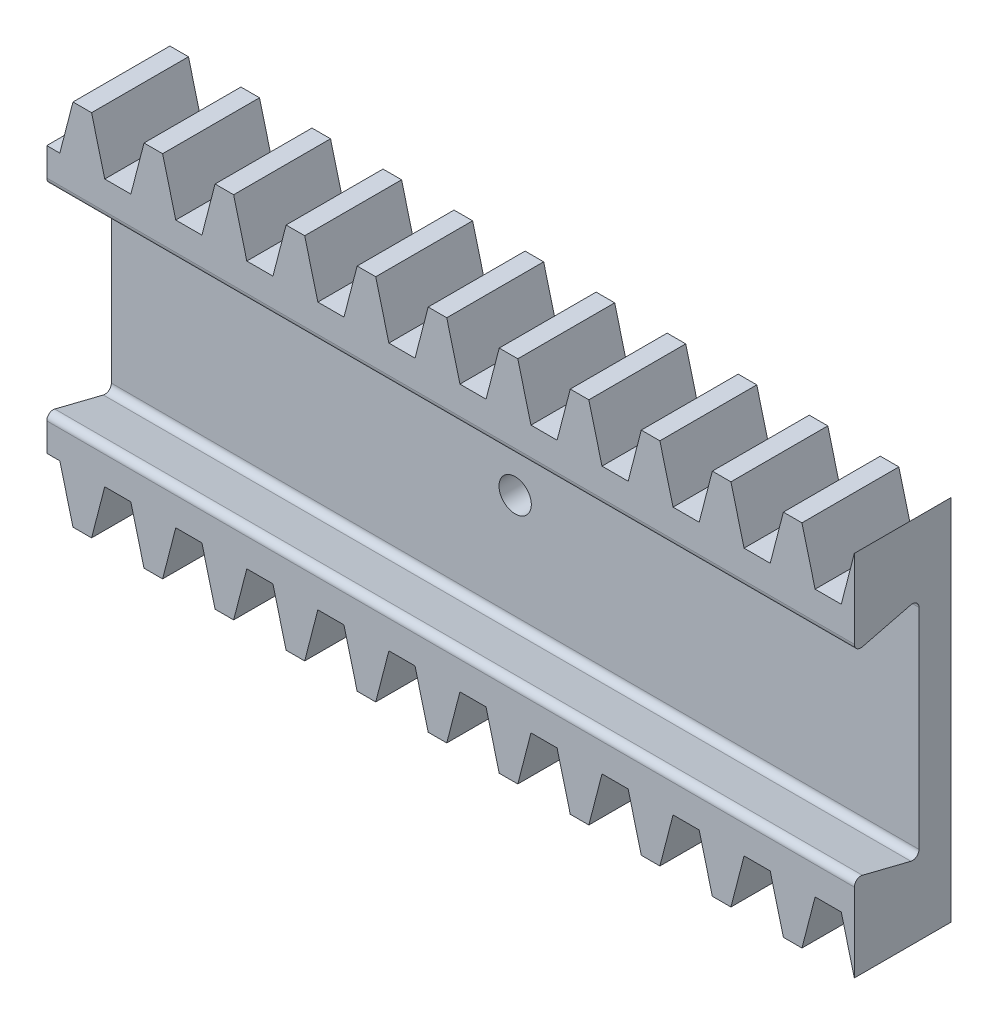
SolidWorks part; units mm, degrees
extrude "Blank" add sketch "BlankSke" against normal blind 3
sketch "BlankSke" plane through (0, 0, 0) normal (0, 0, 1) x (1, 0, 0)
  line L1 (0, 0) -> (25, 0)
  line L2 (0, 0) -> (0, 5.7)
  line L3 (0, 5.7) -> (25, 5.7)
  line L4 (25, 0) -> (25, 5.7)
  dimension "Length" = 25
ref_plane "Plane1" through (0, 0, 0) normal (0, 0, 1) x (1, 0, 0)
ref_plane "Plane2" through (0, 0, 0) normal (0, 1, 0) x (1, 0, 0)
ref_plane "Plane3" through (0, 0, 0) normal (1, 0, 0) x (0, 0, -1)
other "Configuration Table"
sketch "HoldingSke" plane through (0, 0, 0) normal (0, 1, 0) x (1, 0, 0)
  line L0 (0, 0) -> (0.1988, 1.4147)
  line L1 (-15, 0) -> (100, 0) construction
  line L2 (0, 0) -> (-2.1039, 2.3779)
  line L3 (0, 0) -> (-11.863, 4.5341)
  line L4 (0, 0) -> (8.4147, 1.9427)
  line L5 (0, 0) -> (-23.7986, -8.8762)
  line L6 (0, 0) -> (-10.5278, -7.1032)
  line L9 (-67.7845, 28.3722) -> (-43.5808, 34.6317)
  line L10 (-76.2, 3.0779) -> (-71.2, 3.0779)
  line L11 (0, 0) -> (-3, 0)
  line L12 (-76.2, 101.6) -> (-76.173, 101.6)
  line L13 (24.9733, 27.94) -> (52.9518, 28.4284)
  line L14 (24.9733, 27.94) -> (24.9743, 27.94)
  line L15 (24.9733, 27.94) -> (100.4006, 29.5858)
  circle A0 centre (0, 0) radius 19.05
  circle A1 centre (0, 0) radius 2.5
  circle A2 centre (0, 0) radius 12.7
  dimension "Num_teeth" = 13
  dimension "Width" = 3
  dimension "Length" = 25
  dimension "Pitch_height" = 5
sketch "TooCutSkeIll" plane through (0, 0, 0) normal (0, 0, 1) x (1, 0, 0)
  line L0 (-0.8064, 5.679) -> (-0.4386, 4.2569)
  line L1 (-0.2682, 4.125) -> (0.2682, 4.125)
  line L2 (0.4386, 4.2569) -> (0.8064, 5.679)
  line L3 (25, 5.7) -> (0, 5.7) construction
  line L4 (0, 0) -> (0, 64.897) construction
  line L5 (-13.208, 5) -> (12.954, 5) construction
  line L6 (0, 0) -> (25, 0) construction
  line L7 (0.6308, 5) -> (0.6308, 48.7463) construction
  line L8 (-0.6308, 5) -> (-0.6308, 48.7463) construction
  line L9 (0.8335, 5.7) -> (0.8335, 5.7254)
  line L10 (-0.8335, 5.7) -> (-0.8335, 5.7254)
  line L11 (-0.8335, 5.7254) -> (0.8335, 5.7254)
  arc A0 (0.2682, 4.125) -> (0.4386, 4.2569) centre (0.2682, 4.301) ccw
  arc A1 (-0.4386, 4.2569) -> (-0.2682, 4.125) centre (-0.2682, 4.301) ccw
  arc A2 (0.8335, 5.7) -> (0.8064, 5.679) centre (0.8335, 5.672) ccw
  arc A3 (-0.8064, 5.679) -> (-0.8335, 5.7) centre (-0.8335, 5.672) ccw
  dimension "Addendum_plus" = 0.7254
  dimension "Pitch_height" = 5
  dimension "Pressure_angle" = 14.5
  dimension "Gap_width" = 1.2616
  dimension "Dedendum" = 0.875
extrude "ToothCutIll" [suppressed] cut sketch "TooCutSkeIll" against normal through all
sketch "TooCutSkeSim" plane through (0, 0, 0) normal (0, 0, 1) x (1, 0, 0)
  line L0 (0.4045, 4.125) -> (-0.4045, 4.125)
  line L1 (0.8184, 5.7254) -> (0.4045, 4.125)
  line L2 (0, 17.4625) -> (0, 53.467) construction
  line L3 (0.8184, 5.7254) -> (-0.8184, 5.7254)
  line L6 (-0.8184, 5.7254) -> (-0.4045, 4.125)
  line L9 (-0.6308, 5) -> (0.6308, 5) construction
  line L10 (0, 0) -> (25, 0) construction
  line L11 (0.6308, 5) -> (0.6308, 53.467) construction
  line L12 (-0.6308, 5) -> (-0.6308, 53.467) construction
  dimension "Addendum_plus" = 0.7254
  dimension "Pitch_height" = 5
  dimension "Pressure_angle" = 14.5
  dimension "Gap_width" = 1.2616
  dimension "Dedendum" = 0.875
extrude "ToothCutSim" cut sketch "TooCutSkeSim" against normal through all
pattern_linear "TeethCuts" count 13 spacing 2.1991 along (1, 0, 0) of "ToothCutIll", "ToothCutSim"
mirror "镜向1" [suppressed]
mirror "镜向2" about plane through (0, 0, -3) normal (0, -1, 0) of "Blank", "ToothCutSim", "TeethCuts"
sketch "草图1" plane through (0, 0, 0) normal (-1, 0, 0) x (0, 0, 1)
  line L1 (0, 4.125) -> (0, -4.125) construction
  line L4 (-3, 0) -> (0, 0) construction
  line L5 (-3, 4.125) -> (-3, -4.125) construction
  line L7 (0, -3) -> (0, 3)
  line L8 (0, 3) -> (-2, 3.5)
  line L9 (-2, 3.5) -> (-2, -3.5)
  line L10 (0, -3) -> (-2, -3.5)
  point P11 (-2.5, 0)
  point P12 (-2, 0)
  dimension "D1" = 3
  dimension "D2" = 3.5
  dimension "D3" = 2
extrude "切除-拉伸2" cut sketch "草图1" against normal through all
fillet "圆角1" radius 0.2 1 edges at (12.5, -3.5, -2)
fillet "圆角2" radius 0.2 1 edges at (12.5, 3.5, -2)
fillet "圆角3" radius 0.2 2 edges at (12.5, -3, 0) (12.5, 3, 0)
sketch "草图2" plane through (0, 0, -3) normal (0, 0, -1) x (-1, 0, 0)
  line L0 (0, 0) -> (-25, 0) construction
  line L1 (0, 4.125) -> (0, -4.125) construction
  line L2 (-25, -5.692) -> (-25, 5.692) construction
  circle A0 centre (-12.5, 0) radius 1.5
  dimension "D1" = 3
extrude "凸台-拉伸1" add sketch "草图2" along normal blind 1.5
sketch "草图3" plane through (0, 0, -4.5) normal (0, 0, -1) x (-1, 0, 0)
  circle A0 centre (-12.5, 0) radius 0.5
  dimension "D1" = 1
extrude "切除-拉伸3" cut sketch "草图3" against normal through all
equation "' \"Module@HoldingSke\" = 6.35"
equation "' \"Num_teeth@HoldingSke\" = 12"
equation "' \"Ap@HoldingSke\" =  20"
equation "' \"Ap@HoldingSke\" = 20"
equation "' \"Width@HoldingSke\" = 0.25 * 25.4"
equation "' \"Show_teeth@HoldingSke\" = 500"
equation "' \"Backlash@HoldingSke\" = 0.009 * 25.4"
equation "' \"Addendum_fac@HoldingSke\" = 1.0"
equation "' \"Dedendum_fac@HoldingSke\" = 1.25"
equation "' \"Dedendum_add@HoldingSke\" = 0.00005 * 25.4"
equation "' \"Clearance_fac@HoldingSke\" = 0.25"
equation "' \"Pitch_height@HoldingSke\" = 1 * 25.4"
equation "' \"Length@HoldingSke\" = 4.71 * 25.4"
equation "\"Pitch@HoldingSke\" = 1 / \"Module@HoldingSke\""
equation "\"MPH@HoldingSke\" = \"Dedendum_fac@HoldingSke\" / \"Pitch@HoldingSke\" + 2 * \"Dedendum_add@HoldingSke\" + 0.002 * 25.4"
equation "\"MPH@HoldingSke\" = ((sgn( \"MPH@HoldingSke\" - \"Pitch_height@HoldingSke\")+1)*( \"MPH@HoldingSke\" - \"Pitch_height@HoldingSke\"))/2 + \"Pitch_height@HoldingSke\""
equation "\"Blank_height@BlankSke\" = \"Pitch_height@HoldingSke\" + \"Addendum_fac@HoldingSke\"  / \"Pitch@HoldingSke\" "
equation "\"Length@BlankSke\" =  \"Length@HoldingSke\""
equation "\"Face_width@Blank\" = \"Width@HoldingSke\""
equation "\"Pressure_angle@TooCutSkeIll\" = \"Ap@HoldingSke\""
equation "\"Addendum_plus@TooCutSkeIll\" =  \"Addendum_fac@HoldingSke\"  / \"Pitch@HoldingSke\" + 0.001 *25.4"
equation "\"Dedendum@TooCutSkeIll\" = \"Dedendum_fac@HoldingSke\"  / \"Pitch@HoldingSke\""
equation "\"Pitch_height@TooCutSkeIll\" =  \"MPH@HoldingSke\""
equation "\"Gap_width@TooCutSkeIll\" = 3.14159265 / 2 / \"Pitch@HoldingSke\" + 6 * \"Backlash@HoldingSke\""
equation "\"Pressure_angle@TooCutSkeSim\" = \"Ap@HoldingSke\""
equation "\"Addendum_plus@TooCutSkeSim\" =  \"Addendum_fac@HoldingSke\"  / \"Pitch@HoldingSke\" + 0.001 * 25.4"
equation "\"Dedendum@TooCutSkeSim\" = \"Dedendum_fac@HoldingSke\"  / \"Pitch@HoldingSke\""
equation "\"Pitch_height@TooCutSkeSim\" =  \"MPH@HoldingSke\""
equation "\"Gap_width@TooCutSkeSim\" = 3.14159265 / 2 / \"Pitch@HoldingSke\" + 6 * \"Backlash@HoldingSke\""
equation "\"Root_fillet@TooCutSkeIll\" = \"Clearance_fac@HoldingSke\" / \"Pitch@HoldingSke\" + \"Dedendum_add@HoldingSke\""
equation "\"Break_rad@TooCutSkeIll\" = 0.02 / \"Pitch@HoldingSke\" * 2"
equation "\"Linear_pitch@TeethCuts\" = 3.14159265 / \"Pitch@HoldingSke\""
equation "\"Num_teeth@HoldingSke\" = int( ( \"Length@HoldingSke\" + 0 ) / (3.14159265 / \"Pitch@HoldingSke\")) + 0.9999  + 1"
equation " \"Num_teeth@TeethCuts\" = int( \"Show_teeth@HoldingSke\" ) + 1"
equation " \"Num_teeth@TeethCuts\" = ((sgn( \"Num_teeth@TeethCuts\" - \"Num_teeth@HoldingSke\" )-1)*( \"Num_teeth@TeethCuts\" - \"Num_teeth@HoldingSke\" ))/-2+ \"Num_teeth@HoldingSke\""
equation " \"Num_teeth@TeethCuts\" = ((sgn( \"Num_teeth@TeethCuts\" - 2.0)+1)*( \"Num_teeth@TeethCuts\" - 2.0))/2 +2.0"
